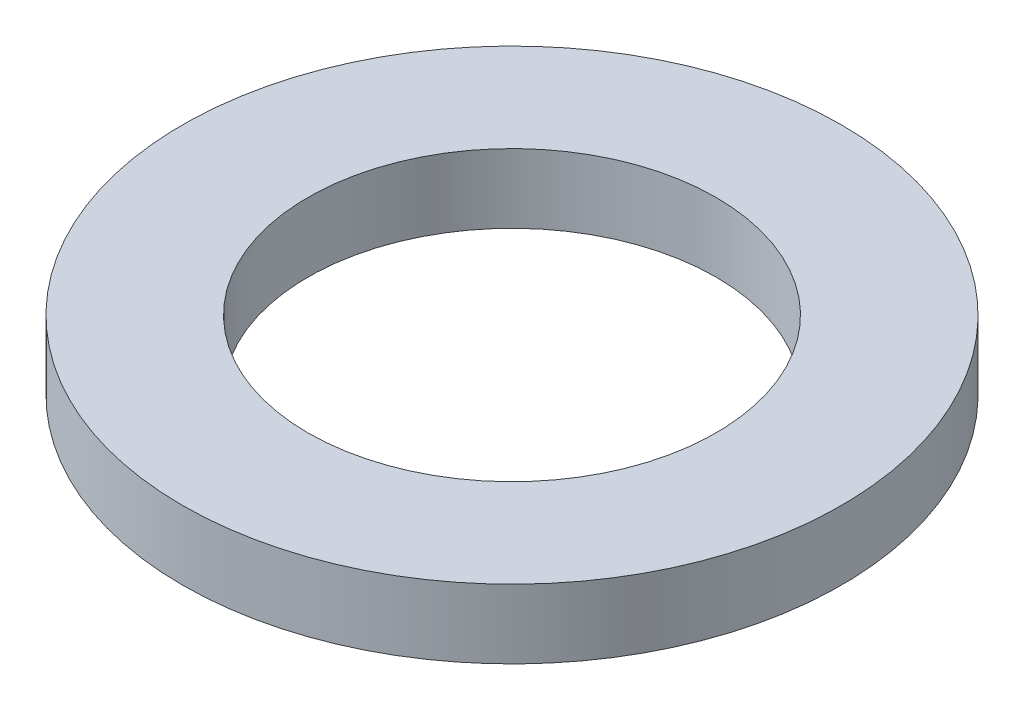
SolidWorks part; units mm, degrees
ref_plane "Front Plane" through (0, 0, 0) normal (0, 0, 1) x (1, 0, 0)
ref_plane "Top Plane" through (0, 0, 0) normal (0, 1, 0) x (1, 0, 0)
ref_plane "Right Plane" through (0, 0, 0) normal (1, 0, 0) x (0, 0, -1)
sketch "Sketch1" plane through (0, 0, 0) normal (0, 1, 0) x (1, 0, 0)
  circle A0 centre (0, 0) radius 52.5
  dimension "FLANGE_OD" = 105
extrude "Boss-Extrude1" add sketch "Sketch1" along normal blind 11
sketch "Sketch2" plane through (0, 0, 0) normal (0, 1, 0) x (1, 0, 0)
  circle A0 centre (0, 0) radius 32.5
  dimension "BORE_D" = 65
extrude "Cut-Extrude1" cut sketch "Sketch2" along normal through all
sketch "Sketch3" plane through (0, 11, 0) normal (0, 1, 0) x (1, 0, 0)
  circle A0 centre (0, 0) radius 22.155 construction
  circle A1 centre (-22.155, 0) radius 3.5915
  dimension "BOLT_D" = 7.1831
  dimension "BOLT_PCD" = 44.31
extrude "Cut-Extrude2" cut sketch "Sketch3" against normal blind 9.109 rebuild error yes
pattern_circular "CirPattern1" count 8 over 360 rebuild error yes
